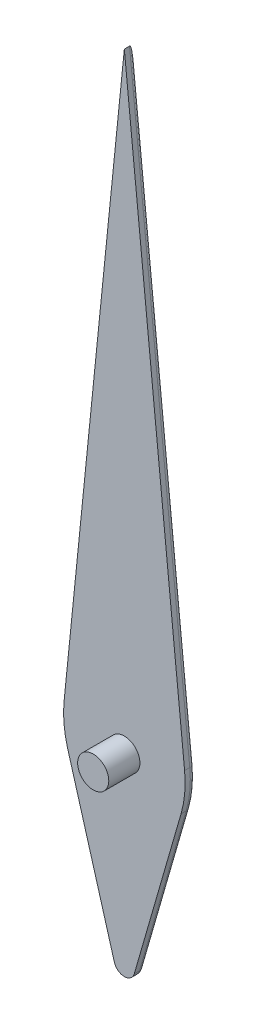
SolidWorks part; units mm, degrees
ref_plane "Front" through (0, 0, 0) normal (0, 0, 1) x (1, 0, 0)
ref_plane "Top" through (0, 0, 0) normal (0, 1, 0) x (1, 0, 0)
ref_plane "Right" through (0, 0, 0) normal (1, 0, 0) x (0, 0, -1)
sketch "Эскиз1" plane through (0, 0, 0) normal (0, 0, 1) x (1, 0, 0)
  line L0 (0, 0) -> (0, 8) construction
  line L1 (0, 8) -> (-0.5805, 2.2698)
  line L2 (-0.5463, 1.8915) -> (0, 0)
  line L3 (0.5463, 1.8915) -> (0, 0)
  line L4 (0, 8) -> (0.5805, 2.2698)
  arc A0 (0.5463, 1.8915) -> (0.5805, 2.2698) centre (-0.4144, 2.169) ccw
  arc A1 (-0.5805, 2.2698) -> (-0.5463, 1.8915) centre (0.4144, 2.169) ccw
  point P7 (0.6, 2.0773)
  point P10 (-0.6, 2.0773)
  dimension "D3" = 1
  dimension "D1" = 8
  dimension "D2" = 0.6
extrude "Бобышка-Вытянуть1" add sketch "Эскиз1" along normal blind 0.1
sketch "Эскиз2" plane through (0, 0, 0.1) normal (0, 0, 1) x (1, 0, 0)
  circle A0 centre (0, 2.1179) radius 0.15
  dimension "D1" = 0.3
extrude "Бобышка-Вытянуть2" add sketch "Эскиз2" along normal blind 0.3
fillet "Скругление1" radius 0.1 1 edges at (0, 0, 0.05)
fillet "Скругление3" radius 0.05 7 edges at (-0.2903, 5.1349, 0) (-0.5815, 2.079, 0) (0.2903, 5.1349, 0) (0.5815, 2.079, 0) (0.3212, 1.1121, 0) (0, 0.2604, 0) (-0.3212, 1.1121, 0)
sketch "Эскиз3" plane through (0, 0, 0) normal (0, 0, -1) x (-1, 0, 0)
  circle A0 centre (0, 2.1179) radius 0.15
extrude "Вырез-Вытянуть1" cut sketch "Эскиз3" against normal blind 0.05
fillet "Скругление4" radius 0.05 1 edges at (-0.15, 2.1179, 0)
